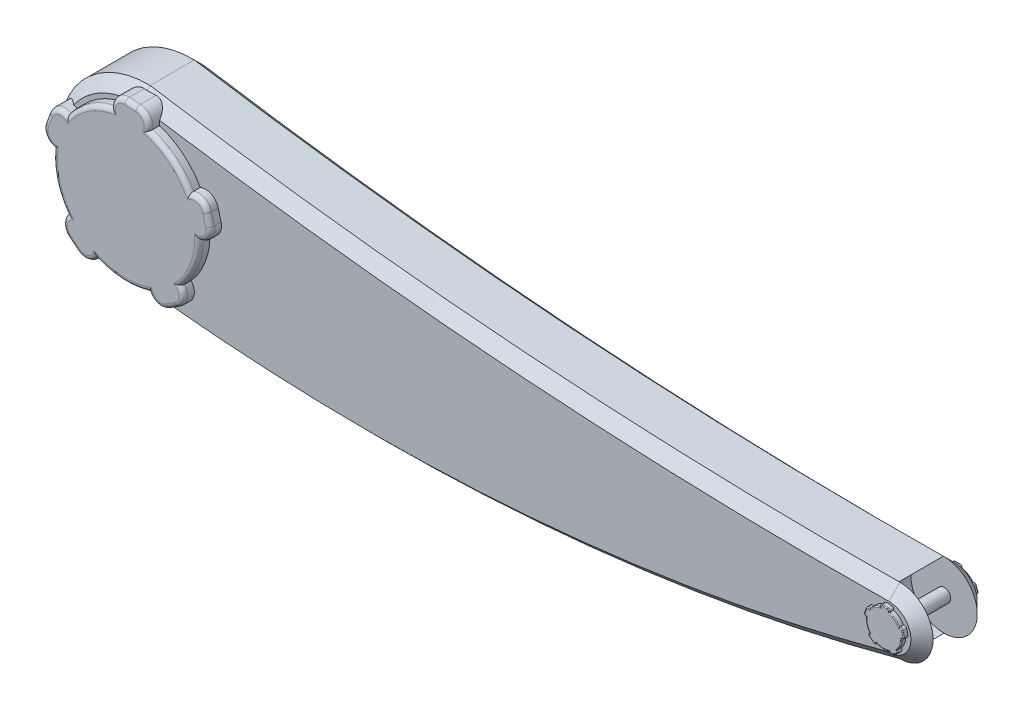
SolidWorks part; units mm, degrees
ref_plane "Front Plane" through (0, 0, 0) normal (0, 0, 1) x (1, 0, 0)
ref_plane "Top Plane" through (0, 0, 0) normal (0, 1, 0) x (1, 0, 0)
ref_plane "Right Plane" through (0, 0, 0) normal (1, 0, 0) x (0, 0, -1)
sketch "Sketch2" plane through (0, 0, 0) normal (0, 0, 1) x (1, 0, 0)
  line L0 (-85, 0) -> (85, 0) construction
  circle A0 centre (85, 0) radius 7.5
  circle A1 centre (-85, 0) radius 20
  arc A2 (85, 7.5) -> (-84.5589, 19.9951) centre (73.4472, 1007.4333) cw
  arc A3 (85, -7.5) -> (-90.7174, -19.1654) centre (-32.0911, 426.9994) cw
  point P4 (0, 0)
  dimension "D2" = 40
  dimension "D3" = 15
  dimension "D4" = 450
  dimension "D5" = 1000
  dimension "D1" = 170
extrude "Boss-Extrude1" add sketch "Sketch2" along normal mid plane 15 contours A1 L0 A0 A2 | L0 A1 A3 A0 | A3 A1 A2 | A0 A2 region at (-6.2658, 5.9616, 0) region at (-84.9993, 0.0082, 0) region at (-3.1686, -10.3297, 0) region at (85, 0, 0)
chamfer "Chamfer1" distance 2.5 angle 45 8 edges at (92.5, 0, -7.5) (-0.0455, 10.1375, -7.5) (-104.7572, 3.1071, -7.5) (-2.2825, -22.0123, -7.5) (-104.7572, 3.1071, 7.5) (-0.0455, 10.1375, 7.5) (92.5, 0, 7.5) (-2.2825, -22.0123, 7.5)
sketch "Sketch3" plane through (0, 0, 7.5) normal (0, 0, 1) x (1, 0, 0)
  circle A0 centre (-85, 0) radius 16.5
  dimension "D1" = 33
extrude "Boss-Extrude2" add sketch "Sketch3" along normal mid plane 5
sketch "Sketch4" plane through (0, 0, 10) normal (0, 0, 1) x (1, 0, 0)
  line L0 (-85, 0) -> (-68.9097, 0)
  line L1 (-66.0119, 3.7765) -> (-66.6676, 6.2235)
  line L2 (-71.0654, 8.0452) -> (-85, 0)
  line L3 (-66.3397, 5) -> (-85, 0) construction
  line L4 (-73.0426, -10.7665) -> (-85, 0)
  line L5 (-85, 0) -> (-80.0278, -15.3028)
  line L6 (-75.5407, -16.8918) -> (-73.416, -15.512)
  line L7 (-91.5445, -14.6992) -> (-85, 0)
  line L8 (-85, 0) -> (-98.0173, -9.4577)
  line L9 (-98.142, -14.2161) -> (-96.1731, -15.8105)
  line L10 (-101.0022, 1.6819) -> (-85, 0)
  line L11 (-85, 0) -> (-98.0173, 9.4577)
  line L12 (-102.5814, 8.1057) -> (-103.4893, 5.7406)
  line L13 (-88.3454, 15.7387) -> (-85, 0)
  line L14 (-85, 0) -> (-80.0278, 15.3028)
  line L15 (-82.724, 19.2257) -> (-85.2539, 19.3583)
  arc A0 (-66.0119, 3.7765) -> (-68.9097, 0) centre (-68.9097, 3) cw
  arc A1 (-66.6676, 6.2235) -> (-71.0654, 8.0452) centre (-69.5654, 5.4471) ccw
  arc A2 (-73.416, -15.512) -> (-73.0426, -10.7665) centre (-75.05, -12.996) ccw
  arc A3 (-75.5407, -16.8918) -> (-80.0278, -15.3028) centre (-77.1746, -14.3758) cw
  arc A4 (-96.1731, -15.8105) -> (-91.5445, -14.6992) centre (-94.2852, -13.479) ccw
  arc A5 (-98.142, -14.2161) -> (-98.0173, -9.4577) centre (-96.254, -11.8847) cw
  arc A6 (-103.4893, 5.7406) -> (-101.0022, 1.6819) centre (-100.6886, 4.6655) ccw
  arc A7 (-102.5814, 8.1057) -> (-98.0173, 9.4577) centre (-99.7807, 7.0306) cw
  arc A8 (-85.2539, 19.3583) -> (-88.3454, 15.7387) centre (-85.4109, 16.3624) ccw
  arc A9 (-82.724, 19.2257) -> (-80.0278, 15.3028) centre (-82.881, 16.2299) cw
  circle A10 centre (-85, 0) radius 2
  point P6 (-65, 0)
  point P11 (-67.6795, 10)
  point P38 (-85, 0)
  circle M27 centre (-85, 0) radius 16.5
  dimension "D4" = 3
  dimension "D6" = 4
  dimension "D1" = 30
  dimension "D2" = 20
  dimension "D3" = 20
  dimension "D5" = 5
extrude "Boss-Extrude3" add sketch "Sketch4" against normal blind 5 contours A10 L14 A9 A8 L13 M27 | A9 L15 A8 M27 | L3 A10 L0 A0 M27 | L3 A1 L2 A10 M27 | L1 L3 A0 M27 | A10 L11 A7 A6 L10 M27 | A10 L8 A5 A4 L7 M27 | A5 L9 A4 M27 | A10 L5 A3 A2 L4 M27 | A3 L6 A2 M27 | L0 A0 L1 A1 L2 | L11 A7 L12 A6 L10 region at (-73.9833, 1.4506, 10) region at (-74.734, 4.2521, 10) region at (-78.9998, -9.2394, 10) region at (-91.9331, -8.5616, 10) region at (-95.285, 3.9481, 10) region at (-84.4234, 11.0017, 10) region at (-67.4332, 2.6871, 10) region at (-75.3796, -14.8141, 10) region at (-96.1162, -13.7273, 10) region at (-84.0756, 17.6395, 10)
fillet "Fillet1" radius 1 20 edges at (-87.5535, 18.4623, 10) (-83.9889, 19.292, 10) (-80.5307, 18.0943, 10) (-74.6162, 12.8229, 10) (-68.2303, 8.1337, 10) (-66.3397, 5, 10) (-66.4102, 1.3409, 10) (-69.5959, -5.9131, 10) (-72.0823, -13.4355, 10) (-74.4784, -16.2019, 10) (-77.9802, -17.2656, 10) (-85.8635, -16.4774, 10) (-93.7861, -16.4372, 10) (-97.1575, -15.0133, 10) (-99.2513, -12.0116, 10) (-100.9378, -4.2705, 10) (-103.3478, 3.2767, 10) (-103.0354, 6.9231, 10) (-100.8276, 9.842, 10) (-93.9865, 13.8381, 10)
sketch "Sketch6" plane through (0, 0, -7.5) normal (0, 0, -1) x (-1, 0, 0)
  circle A0 centre (85, 0) radius 5
  dimension "D1" = 10
extrude "Boss-Extrude4" add sketch "Sketch6" along normal blind 10
sketch "Sketch7" plane through (0, 0, -7.5) normal (0, 0, -1) x (-1, 0, 0)
  circle A0 centre (-85, 0) radius 7.5
extrude "Cut-Extrude1" cut sketch "Sketch7" along direction (0, 0, 1) on the side against the normal blind 10 from offset 2.5 offset against normal yes
sketch "Sketch8" plane through (0, 0, -7.5) normal (0, 0, -1) x (-1, 0, 0)
  circle A0 centre (-85, 0) radius 1.5
extrude "Boss-Extrude5" add sketch "Sketch8" against normal blind 14 contours A0
sketch "Sketch10" plane through (0, 0, -7.5) normal (0, 0, -1) x (-1, 0, 0)
  line L1 (-80.3747, 0.6353) -> (-80.6701, 1.7247)
  line L4 (-85.013, 5) -> (-84.9976, 4.5083) construction
  line L7 (-82.8721, -4.0638) -> (-81.9273, -3.4462)
  line L11 (-88.1129, -3.1407) -> (-87.2336, -3.8484)
  line L15 (-88.8546, 2.1289) -> (-89.2559, 1.0739)
  line L19 (-84.0721, 4.4626) -> (-85.1994, 4.5182)
  line L25 (-84.7326, -3.9936) -> (-84.7016, -4.9911) construction
  arc A0 (-80.3747, 0.6353) -> (-80.8573, 0.0044) centre (-80.8573, 0.5044) cw
  arc A1 (-80.6701, 1.7247) -> (-81.4053, 2.0253) centre (-81.1527, 1.5938) ccw
  arc A2 (-84.7016, -4.9911) -> (90.1876, -16.7134) centre (32.0911, 426.9994) ccw construction
  arc A3 (-85.013, 5) -> (-84.7016, -4.9911) centre (-85, 0) ccw construction
  arc A4 (-82.8721, -4.0638) -> (-83.6212, -3.7998) centre (-83.1457, -3.6453) cw
  arc A5 (-81.9273, -3.4462) -> (-81.8686, -2.6541) centre (-82.2009, -3.0277) ccw
  arc A6 (-88.1129, -3.1407) -> (-88.0933, -2.3467) centre (-87.7994, -2.7512) cw
  arc A7 (-87.2336, -3.8484) -> (-86.4621, -3.6595) centre (-86.9201, -3.4589) ccw
  arc A8 (-88.8546, 2.1289) -> (-88.0933, 2.3556) centre (-88.3872, 1.9511) cw
  arc A9 (-89.2559, 1.0739) -> (-88.8378, 0.3985) centre (-88.7885, 0.8961) ccw
  arc A10 (-84.0721, 4.4626) -> (-83.6212, 3.8087) centre (-84.0967, 3.9632) cw
  arc A11 (-85.1994, 4.5182) -> (-85.7125, 3.9119) centre (-85.2241, 4.0189) ccw
  arc A12 (-88.8378, 0.3985) -> (-88.0933, -2.3467) centre (-84.8573, 0.0044) ccw
  arc A13 (-85.7125, 3.9119) -> (-88.0933, 2.3556) centre (-84.8573, 0.0044) ccw
  arc A14 (-81.4053, 2.0253) -> (-83.6212, 3.8087) centre (-84.8573, 0.0044) ccw
  arc A15 (-81.8686, -2.6541) -> (-80.8573, 0.0044) centre (-84.8573, 0.0044) ccw
  arc A16 (-86.4621, -3.6595) -> (-83.6212, -3.7998) centre (-84.8573, 0.0044) ccw
  point P48 (-84.8573, 0.0044)
  dimension "D1" = 5
extrude "Boss-Extrude6" add sketch "Sketch10" along direction (0, 0, -1) on the side of the normal blind 1
sketch "Sketch11" plane through (0, 0, 7.5) normal (0, 0, 1) x (1, 0, 0)
  line L0 (89.3398, 0.6353) -> (89.0444, 1.7247)
  line L1 (84.7016, 5) -> (84.7169, 4.5083) construction
  line L2 (86.8424, -4.0638) -> (87.7872, -3.4462)
  line L3 (81.6016, -3.1407) -> (82.4809, -3.8484)
  line L4 (80.86, 2.1289) -> (80.4587, 1.0739)
  line L5 (85.6425, 4.4626) -> (84.5151, 4.5182)
  line L6 (84.9819, -3.9936) -> (85.013, -4.9911) construction
  arc A0 (89.3398, 0.6353) -> (88.8573, 0.0044) centre (88.8573, 0.5044) cw
  arc A1 (89.0444, 1.7247) -> (88.3092, 2.0253) centre (88.5618, 1.5938) ccw
  arc A2 (86.8424, -4.0638) -> (86.0933, -3.7998) centre (86.5689, -3.6453) cw
  arc A3 (87.7872, -3.4462) -> (87.846, -2.6541) centre (87.5136, -3.0277) ccw
  arc A4 (81.6016, -3.1407) -> (81.6212, -2.3467) centre (81.9151, -2.7512) cw
  arc A5 (82.4809, -3.8484) -> (83.2524, -3.6595) centre (82.7944, -3.4589) ccw
  arc A6 (80.86, 2.1289) -> (81.6212, 2.3556) centre (81.3273, 1.9511) cw
  arc A7 (80.4587, 1.0739) -> (80.8767, 0.3985) centre (80.926, 0.8961) ccw
  arc A8 (85.6425, 4.4626) -> (86.0933, 3.8087) centre (85.6178, 3.9632) cw
  arc A9 (84.5151, 4.5182) -> (84.002, 3.9119) centre (84.4904, 4.0189) ccw
  arc A10 (80.8767, 0.3985) -> (81.6212, -2.3467) centre (84.8573, 0.0044) ccw
  arc A11 (84.002, 3.9119) -> (81.6212, 2.3556) centre (84.8573, 0.0044) ccw
  arc A12 (88.3092, 2.0253) -> (86.0933, 3.8087) centre (84.8573, 0.0044) ccw
  arc A13 (87.846, -2.6541) -> (88.8573, 0.0044) centre (84.8573, 0.0044) ccw
  arc A14 (83.2524, -3.6595) -> (86.0933, -3.7998) centre (84.8573, 0.0044) ccw
  point P34 (95.0655, 0.3878)
extrude "Boss-Extrude7" add sketch "Sketch11" along normal blind 1
fillet "Fillet2" radius 0.2 40 edges at (81.1186, -1.4177, -8.5) (81.7023, -3.0646, -8.5) (82.3997, -3.755, -8.5) (83.3119, -4.1168, -8.5) (85.0545, -3.9907, -8.5) (86.8012, -3.9445, -8.5) (87.6733, -3.4946, -8.5) (88.2993, -2.7389, -8.5) (88.7178, -1.0425, -8.5) (89.2137, 0.6329, -8.5) (89.0552, 1.6014, -8.5) (88.53, 2.4303, -8.5) (87.0459, 3.3525, -8.5) (85.6058, 4.3418, -8.5) (84.6358, 4.4904, -8.5) (83.6851, 4.247, -8.5) (82.3494, 3.1206, -8.5) (80.9635, 2.0567, -8.5) (80.5224, 1.18, -8.5) (80.4601, 0.2007, -8.5) (88.5959, -1.4177, 8.5) (88.0123, -3.0646, 8.5) (87.3148, -3.755, 8.5) (86.4027, -4.1168, 8.5) (84.66, -3.9907, 8.5) (82.9134, -3.9445, 8.5) (82.0413, -3.4946, 8.5) (81.4152, -2.7389, 8.5) (80.9967, -1.0425, 8.5) (80.5009, 0.6329, 8.5) (80.6593, 1.6014, 8.5) (81.1846, 2.4303, 8.5) (82.6686, 3.3525, 8.5) (84.1088, 4.3418, 8.5) (85.0788, 4.4904, 8.5) (86.0294, 4.247, 8.5) (87.3651, 3.1206, 8.5) (88.7511, 2.0567, 8.5) (89.1921, 1.18, 8.5) (89.2544, 0.2007, 8.5)
